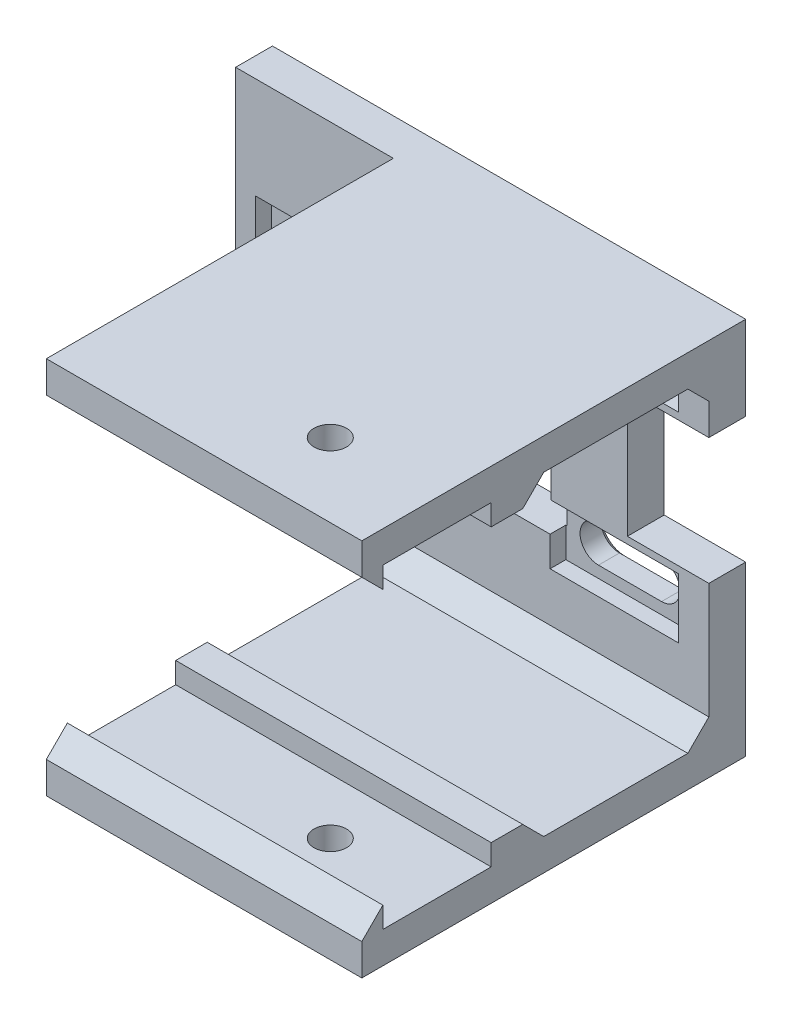
SolidWorks part; units mm, degrees
note: '?' marks a value the reader was unsure of.
ref_plane "Front" through (0, 0, 0) normal (0, 0, 1) x (1, 0, 0)
ref_plane "Top" through (0, 0, 0) normal (0, 1, 0) x (1, 0, 0)
ref_plane "Right" through (0, 0, 0) normal (1, 0, 0) x (0, 0, -1)
sketch "Sketch1" plane through (0, 0, 0) normal (0, 0, 1) x (1, 0, 0)
  line L1 (0, 0) -> (50, 0)
  line L2 (0, 0) -> (0, 36)
  line L3 (0, 36) -> (50, 36)
  line L4 (50, 0) -> (50, 36)
  dimension "D1" = 36
  dimension "D2" = 50
extrude "Boss-Extrude1" add sketch "Sketch1" along normal blind 4
sketch "Sketch2" plane through (0, 0, 0) normal (0, 0, -1) x (-1, 0, 0)
  line L0 (0, 0) -> (-50, 0) construction
  line L1 (-50, 33) -> (-20, 33)
  line L2 (-50, 33) -> (-50, 36)
  line L3 (-50, 36) -> (-20, 36)
  line L4 (-20, 33) -> (-20, 36)
  line L5 (-50, 3) -> (-20, 3)
  line L6 (-50, 3) -> (-50, 0)
  line L7 (-50, 0) -> (-20, 0)
  line L8 (-20, 3) -> (-20, 0)
  line L9 (-50, 36) -> (0, 36) construction
  dimension "D1" = 3
  dimension "D2" = 3
  dimension "D3" = 30
extrude "Boss-Extrude2" add sketch "Sketch2" against normal blind 37
sketch "Sketch3" plane through (0, 36, 0) normal (0, 1, 0) x (1, 0, 0)
  line L0 (20, -37) -> (50, -37) construction
  line L1 (50, -37) -> (50, 0) construction
  circle A0 centre (40, -30) radius 1.55
  dimension "D3" = 3.1
  dimension "D1" = 7
  dimension "D2" = 10
extrude "Cut-Extrude1" cut sketch "Sketch3" against normal through all
sketch "Sketch4" plane through (0, 0, 0) normal (0, 0, -1) x (-1, 0, 0)
  line L0 (-50, 0) -> (-50, 36) construction
  line L1 (-35, 23.5) -> (-19, 23.5)
  line L2 (-35, 23.5) -> (-35, 12.5)
  line L3 (-35, 12.5) -> (-19, 12.5)
  line L4 (-19, 23.5) -> (-19, 12.5)
  point P6 (-35, 18)
  point P7 (-50, 18)
  dimension "D1" = 11
  dimension "D2" = 15
  dimension "D3" = 16
extrude "Cut-Extrude2" cut sketch "Sketch4" against normal blind 10
sketch "Sketch5" plane through (0, 0, 0) normal (0, 0, -1) x (-1, 0, 0)
  line L0 (-44, 12.5) -> (-38, 12.5) construction
  line L1 (-44, 14.25) -> (-38, 14.25)
  line L2 (-44, 10.75) -> (-38, 10.75)
  line L4 (-35, 23.5) -> (-35, 12.5) construction
  line L5 (-35, 12.5) -> (-19, 12.5) construction
  arc A0 (-44, 14.25) -> (-44, 10.75) centre (-44, 12.5) ccw
  arc A1 (-38, 10.75) -> (-38, 14.25) centre (-38, 12.5) ccw
  point P2 (-41, 12.5)
  dimension "D1" = 3.5
  dimension "D2" = 6
  dimension "D3" = 3
extrude "Cut-Extrude3" cut sketch "Sketch5" against normal blind 10
ref_plane "Plane1" through (0, 12.5, 0) normal (0, 1, 0) x (1, 0, 0)
ref_plane "Plane2" through (0, 22, 0) normal (0, 1, 0) x (1, 0, 0)
mirror "Mirror1" about plane through (0, 22, 0) normal (0, 1, 0) of "Cut-Extrude3"
sketch "Sketch6" plane through (0, 0, 0) normal (0, 0, -1) x (-1, 0, 0)
  line L1 (-42.25, 16) -> (-62.25, 16)
  line L2 (-42.25, 16) -> (-42.25, 28)
  line L3 (-42.25, 28) -> (-62.25, 28)
  line L4 (-62.25, 16) -> (-62.25, 28)
  line L5 (1.65, 22) -> (-1.65, 22) construction
  arc A0 (-38, 10.75) -> (-38, 14.25) centre (-38, 12.5) ccw construction
  dimension "D1" = 4.25
  dimension "D2" = 12
  dimension "D3" = 6
  dimension "D4" = 20
extrude "Cut-Extrude4" cut sketch "Sketch6" against normal blind 8
ref_plane "Plane3" through (27, 0, 0) normal (-1, 0, 0) x (0, 0, 1)
sketch "Sketch7" plane through (0, 3, 0) normal (0, 1, 0) x (1, 0, 0)
  line L0 (20, -37) -> (20, -4) construction
  line L1 (20, -21.7) -> (50, -21.7)
  line L2 (20, -21.7) -> (20, -24.7)
  line L3 (20, -24.7) -> (50, -24.7)
  line L4 (50, -21.7) -> (50, -24.7)
  line L5 (50, -37) -> (50, 0) construction
  line L6 (20, -37) -> (50, -37) construction
  dimension "D1" = 12.3
  dimension "D2" = 3
extrude "Boss-Extrude3" add sketch "Sketch7" along normal blind 2
ref_plane "Plane4" through (0, 18, 0) normal (0, 1, 0) x (1, 0, 0)
mirror "Mirror3" about plane through (0, 18, 0) normal (0, 1, 0) of "Boss-Extrude3"
chamfer "Chamfer1" distance 2 angle 45 2 edges at (35, 33, 21.7) (35, 3, 21.7)
ref_axis "Axis1" through (27, 18, 1.4) along (0, 0, 1)?
pattern_circular "CirPattern1" count 2 over 360 about axis through (27, 18, 0) along (0, 0, 1) of "Cut-Extrude3", "Cut-Extrude4", "Mirror1"
sketch "Sketch9" plane through (0, 0, 0) normal (0, 0, -1) x (-1, 0, 0)
  line L0 (0, 0) -> (-50, 0) construction
  line L1 (0, 36) -> (-5, 36)
  line L2 (0, 36) -> (0, 0)
  line L3 (0, 0) -> (-5, 0)
  line L4 (-5, 36) -> (-5, 0)
  dimension "D1" = 5
extrude "Cut-Extrude6" cut sketch "Sketch9" against normal blind 10
chamfer "Chamfer2" distance 0.5 angle 45 31 edges at (17.75, 4.5, 0) (13, 2.75, 0) (8.25, 4.5, 0) (13, 6.25, 0) (36.25, 31.5, 0) (41, 33.25, 0) (45.75, 31.5, 0) (41, 29.75, 0) (27, 12.5, 0) (19, 18, 0) (27, 23.5, 0) (35, 18, 0) (41, 10.75, 0) (36.25, 12.5, 0) (41, 14.25, 0) (45.75, 12.5, 0) (13, 25.25, 0) (17.75, 23.5, 0) (13, 21.75, 0) (8.25, 23.5, 0) (8.375, 20, 0) (11.75, 14, 0) (8.375, 8, 0) (5, 4, 0) (27.5, 0, 0) (50, 32, 0) (46.125, 16, 0) (42.25, 22, 0) (46.125, 28, 0) (27.5, 36, 0) (5, 28, 0)
sketch "Sketch10" plane through (0, 3, 0) normal (0, 1, 0) x (1, 0, 0)
  line L0 (50, -37) -> (50, -0.5) construction
  line L1 (20, -37) -> (50, -37)
  line L2 (20, -37) -> (20, -35)
  line L3 (20, -35) -> (50, -35)
  line L4 (50, -37) -> (50, -35)
  dimension "D1" = 2
extrude "Boss-Extrude4" add sketch "Sketch10" along normal blind 2
mirror "Mirror4" about plane through (0, 18, 0) normal (0, 1, 0) of "Boss-Extrude4"
chamfer "Chamfer3" distance 2 angle 45 2 edges at (35, 31, 37) (35, 5, 37)
sketch "Sketch12" plane through (0, 0, 4) normal (0, 0, 1) x (1, 0, 0)
  line L6 (19.1, 20.65) -> (6.9, 20.65)
  line L7 (19.1, 20.65) -> (19.1, 26.35)
  line L8 (19.1, 26.35) -> (6.9, 26.35)
  line L9 (6.9, 20.65) -> (6.9, 26.35)
  arc A0 (16, 21.75) -> (16, 25.25) centre (16, 23.5) ccw construction
  arc A2 (10, 25.25) -> (10, 21.75) centre (10, 23.5) ccw construction
  dimension "D2" = 3.1
  dimension "D3" = 2.85
  dimension "D4" = 3.1
  dimension "D1" = 5.7
extrude "Cut-Extrude7" cut sketch "Sketch12" against normal blind 1.5 and the other way up to surface (6 mm away) other way up to face at (41, 33.1557, 10)
ref_plane "Plane5" through (0, 14, 0) normal (0, -1, 0) x (-1, 0, 0)
mirror "Mirror5" about plane through (0, 14, 0) normal (0, -1, 0) of "Cut-Extrude7"
pattern_circular "CirPattern2" count 2 over 360 about axis through (27, 18, 0) along (0, 0, 1) of "Mirror5", "Cut-Extrude7"
chamfer "Chamfer4" distance 2 angle 45 3 edges at (48.55, 33, 4) (35, 3, 4) (27.45, 33, 4)
